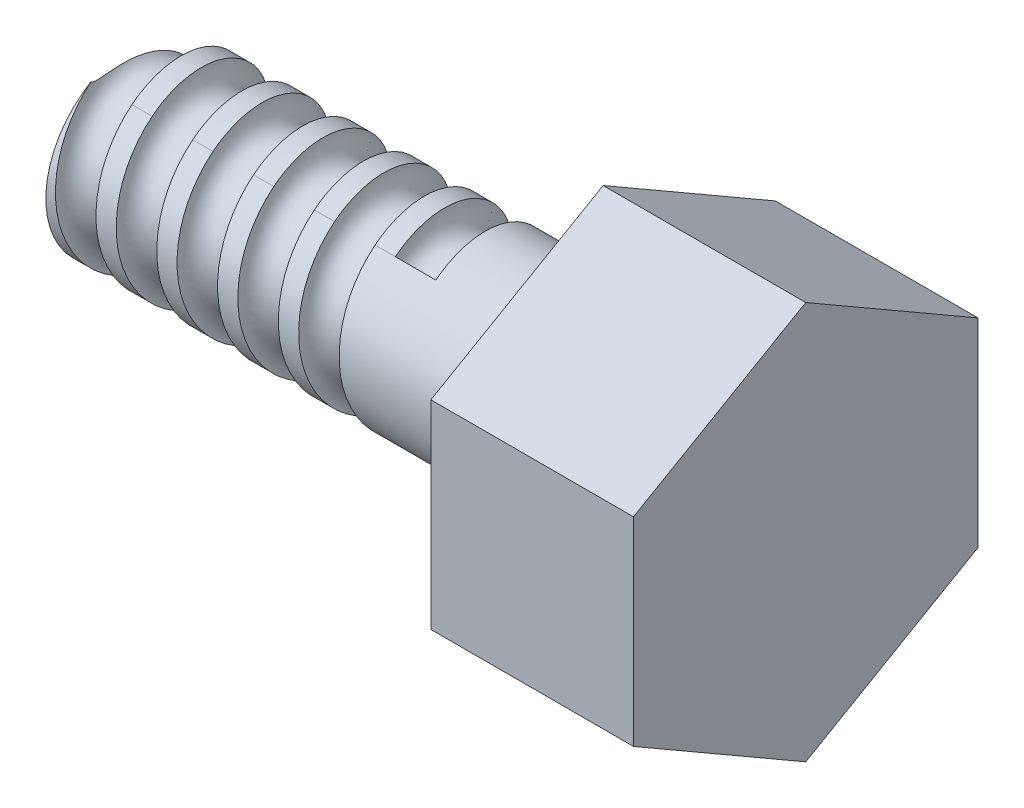
SolidWorks part; units mm, degrees
ref_plane "正面" through (0, 0, 0) normal (0, 0, 1) x (1, 0, 0)
ref_plane "平面" through (0, 0, 0) normal (0, 1, 0) x (1, 0, 0)
ref_plane "右側面" through (0, 0, 0) normal (1, 0, 0) x (0, 0, -1)
sketch "ｽｹｯﾁ1" plane through (0, 0, 0) normal (1, 0, 0) x (0, 0, -1)
  line L0 (0, 9.815) -> (0, -9.815) construction
  line L2 (0, -9.815) -> (8.5, -4.9075)
  line L3 (8.5, -4.9075) -> (8.5, 4.9075)
  line L4 (8.5, 4.9075) -> (0, 9.815)
  line L5 (0, 9.815) -> (-8.5, 4.9075)
  line L6 (-8.5, 4.9075) -> (-8.5, -4.9075)
  line L7 (-8.5, -4.9075) -> (0, -9.815)
  circle A0 centre (0, 0) radius 8.5 construction
  dimension "D1" = 8.5
  dimension "D2" = 8.5
extrude "ﾎﾞｽ - 押し出し3" add sketch "ｽｹｯﾁ1" along normal blind 10
sketch "ｽｹｯﾁ3" plane through (0, 0, 0) normal (-1, 0, 0) x (0, 0, 1)
  circle A0 centre (0, 0) radius 4.5
  dimension "D1" = 9
extrude "ﾎﾞｽ - 押し出し4" add sketch "ｽｹｯﾁ3" along normal blind 23
sketch "ｽｹｯﾁ4" plane through (-23, 0, 0) normal (-1, 0, 0) x (0, 0, 1)
  circle A0 centre (0, 0) radius 4.5
  dimension "D1" = 9
curve "ﾍﾘｶﾙ ｶｰﾌﾞ/ｽﾊﾟｲﾗﾙ ｶｰﾌﾞ2" pitch 3 height 16 radius 4.5 centre (-23, 0, 0) axis (1, 0, 0) start towards (0, 0, -1)
ref_plane "平面2" through (0, 0, 0) normal (0, 1, 0) x (1, 0, 0)
sketch "ｽｹｯﾁ27" plane through (0, 0, 0) normal (0, 1, 0) x (1, 0, 0)
  circle A0 centre (-23, 4.5) radius 1
  dimension "D1" = 2
sweep "ｶｯﾄ - ｽｲｰﾌﾟ5" cut profiles "ｽｹｯﾁ27" path "ﾍﾘｶﾙ ｶｰﾌﾞ/ｽﾊﾟｲﾗﾙ ｶｰﾌﾞ2" align with end faces yes
